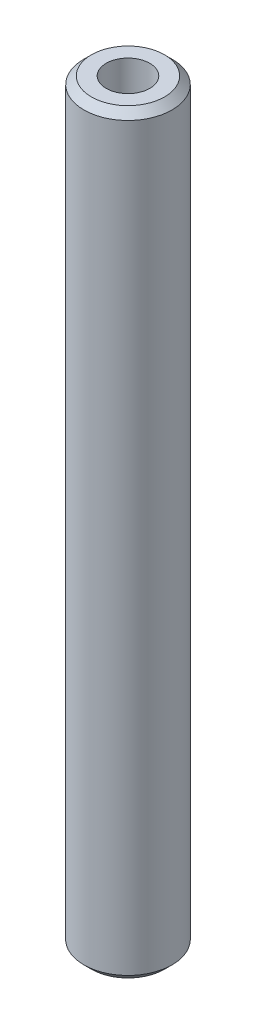
SolidWorks part; units mm, degrees
ref_plane "Front Plane" through (0, 0, 0) normal (0, 0, 1) x (1, 0, 0)
ref_plane "Top Plane" through (0, 0, 0) normal (0, 1, 0) x (1, 0, 0)
ref_plane "Right Plane" through (0, 0, 0) normal (1, 0, 0) x (0, 0, -1)
sketch "Sketch1" plane through (0, 0, 0) normal (0, 1, 0) x (1, 0, 0)
  circle A0 centre (0, 0) radius 35
  dimension "SHAFT_OD" = 70
extrude "Boss-Extrude1" add sketch "Sketch1" along normal blind 600
sketch "Sketch2" plane through (0, 0, 0) normal (0, 1, 0) x (1, 0, 0)
  circle A0 centre (0, 0) radius 17.3093
  dimension "BORE_D" = 34.6186
extrude "Cut-Extrude1" cut sketch "Sketch2" along normal through all
chamfer "Chamfer1" distance 5.9735 angle 45 2 edges at (0, 600, 35) (0, 0, 35)
